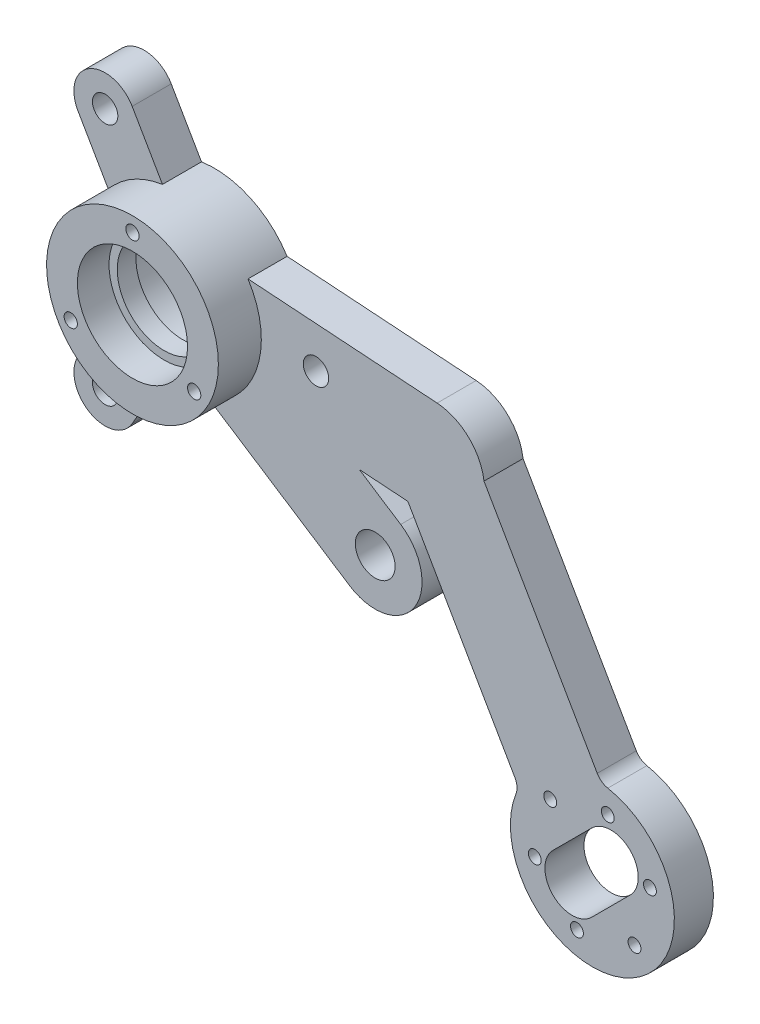
SolidWorks part; units mm, degrees
ref_plane "Front Plane" through (0, 0, 0) normal (0, 0, 1) x (1, 0, 0)
ref_plane "Top Plane" through (0, 0, 0) normal (0, 1, 0) x (1, 0, 0)
ref_plane "Right Plane" through (0, 0, 0) normal (1, 0, 0) x (0, 0, -1)
sketch "S01 - Bearing barrel" plane through (0, 0, 0) normal (0, 0, 1) x (1, 0, 0)
  circle A0 centre (0, 0) radius 22
  dimension "D1" = 44
extrude "01 - Bearing barrel" add sketch "S01 - Bearing barrel" along normal blind 21
sketch "S02 - Torque arm 1" plane through (0, 0, 0) normal (0, 0, 1) x (1, 0, 0)
  line L0 (0, 8) -> (36, 8)
  line L1 (36, -8) -> (0, -8)
  arc A0 (36, 8) -> (36, -8) centre (36, 0) cw
  arc A1 (0, -8) -> (0, 8) centre (0, 0) cw
  dimension "D1" = 8
  dimension "D2" = 36
extrude "02 - Torque arm 1" add sketch "S02 - Torque arm 1" along normal blind 10
sketch "S03 - Torque arm 2" plane through (0, 0, 0) normal (0, 0, 1) x (1, 0, 0)
  line L0 (-6.9282, -4) -> (-24.9282, 27.1769)
  line L1 (-11.0718, 35.1769) -> (6.9282, 4)
  arc A0 (-24.9282, 27.1769) -> (-11.0718, 35.1769) centre (-18, 31.1769) cw
  arc A1 (6.9282, 4) -> (-6.9282, -4) centre (0, 0) cw
  dimension "D1" = 8
  dimension "D2" = 8
  dimension "D3" = 6.9282
  dimension "D4" = 6.9282
  dimension "D5" = 11.0718
  dimension "D6" = 18
  dimension "D7" = 24.9282
  dimension "D8" = 27.1769
extrude "03 - Torque arm 2" add sketch "S03 - Torque arm 2" along normal blind 10
sketch "S04 - Torque arm 3" plane through (0, 0, 0) normal (0, 0, 1) x (1, 0, 0)
  line L0 (6.9282, -4) -> (-11.0718, -35.1769)
  line L1 (-24.9282, -27.1769) -> (-6.9282, 4)
  arc A0 (-11.0718, -35.1769) -> (-24.9282, -27.1769) centre (-18, -31.1769) cw
  arc A1 (-6.9282, 4) -> (6.9282, -4) centre (0, 0) cw
  dimension "D1" = 8
  dimension "D2" = 8
  dimension "D3" = 6.9282
  dimension "D4" = 6.9282
  dimension "D5" = 11.0718
  dimension "D6" = 18
  dimension "D7" = 24.9282
  dimension "D8" = 27.1769
extrude "04 - Torque arm 3" add sketch "S04 - Torque arm 3" along normal blind 10
sketch "S05 - Wheel arm root to rounded elbow" plane through (0, 0, 0) normal (0, 0, 1) x (1, 0, 0)
  line L0 (0.8909, 12.9694) -> (67.0223, 8.4265)
  line L1 (65.2405, -17.5124) -> (-0.8909, -12.9694)
  arc A0 (67.0223, 8.4265) -> (65.2405, -17.5124) centre (66.1314, -4.5429) cw
  arc A1 (-0.8909, -12.9694) -> (0.8909, 12.9694) centre (0, 0) cw
  dimension "D1" = 13
  dimension "D2" = 13
  dimension "D3" = 0.8909
  dimension "D4" = 65.2405
  dimension "D5" = 66.1314
  dimension "D6" = 67.0223
  dimension "D7" = 0.8909
  dimension "D8" = 8.4265
extrude "05 - Wheel arm root to rounded elbow" add sketch "S05 - Wheel arm root to rounded elbow" along normal blind 10
sketch "S06 - Long dropped wheel arm" plane through (0, 0, 0) normal (0, 0, 1) x (1, 0, 0)
  line L0 (76.5281, 1.4494) -> (116.8865, -68.5726)
  line L1 (96.093, -80.5573) -> (55.7347, -10.5353)
  arc A0 (116.8865, -68.5726) -> (96.093, -80.5573) centre (106.4898, -74.5649) cw
  arc A1 (55.7347, -10.5353) -> (76.5281, 1.4494) centre (66.1314, -4.5429) cw
  dimension "D1" = 12
  dimension "D2" = 12
  dimension "D3" = 55.7347
  dimension "D4" = 66.1314
  dimension "D5" = 76.5281
  dimension "D6" = 96.093
  dimension "D7" = 106.4898
  dimension "D8" = 116.8865
  dimension "D9" = 1.4494
  dimension "D10" = 68.5726
extrude "06 - Long dropped wheel arm" add sketch "S06 - Long dropped wheel arm" along normal blind 10
sketch "S07 - Broad cam follower mounting lug" plane through (0, 0, 0) normal (0, 0, 1) x (1, 0, 0)
  line L0 (6.5357, 10.064) -> (57.6946, -23.1589)
  line L1 (44.6232, -43.287) -> (-6.5357, -10.064)
  arc A0 (57.6946, -23.1589) -> (44.6232, -43.287) centre (51.1589, -33.223) cw
  arc A1 (-6.5357, -10.064) -> (6.5357, 10.064) centre (0, 0) cw
  dimension "D1" = 12
  dimension "D2" = 12
  dimension "D3" = 6.5357
  dimension "D4" = 44.6232
  dimension "D5" = 51.1589
  dimension "D6" = 57.6946
  dimension "D7" = 6.5357
  dimension "D8" = 23.1589
extrude "07 - Broad cam follower mounting lug" add sketch "S07 - Broad cam follower mounting lug" along normal blind 10
sketch "S08 - Bearing through relief" plane through (0, 0, 0) normal (0, 0, 1) x (1, 0, 0)
  circle A0 centre (0, 0) radius 12
  dimension "D1" = 24
extrude "08 - Bearing through relief" cut sketch "S08 - Bearing through relief" along normal blind 23 from offset 1 offset against normal yes
sketch "S09 - Inboard 6001 seat" plane through (0, 0, 0) normal (0, 0, 1) x (1, 0, 0)
  circle A0 centre (0, 0) radius 14.1
  dimension "D1" = 28.2
extrude "09 - Inboard 6001 seat" cut sketch "S09 - Inboard 6001 seat" along normal blind 8.2 from offset 0.1 offset against normal yes
sketch "S10 - Outboard 6001 seat" plane through (0, 0, 0) normal (0, 0, 1) x (1, 0, 0)
  circle A0 centre (0, 0) radius 14.1
  dimension "D1" = 28.2
extrude "10 - Outboard 6001 seat" cut sketch "S10 - Outboard 6001 seat" along normal blind 8.2 from offset 12.9
sketch "S11 - Keeper screws" plane through (0, 0, 0) normal (0, 0, 1) x (1, 0, 0)
  circle A0 centre (0, 18.25) radius 1.7
  circle A1 centre (-15.805, -9.125) radius 1.7
  circle A2 centre (15.805, -9.125) radius 1.7
  dimension "D1" = 3.4
  dimension "D2" = 3.4
  dimension "D3" = 3.4
  dimension "D4" = 15.805
  dimension "D5" = 15.805
  dimension "D6" = 18.25
  dimension "D7" = 9.125
extrude "11 - Keeper screws" cut sketch "S11 - Keeper screws" along normal blind 23 from offset 1 offset against normal yes
sketch "S12 - Torque pin retaining stems" plane through (0, 0, 0) normal (0, 0, 1) x (1, 0, 0)
  circle A0 centre (36, 0) radius 3.25
  circle A1 centre (-18, 31.1769) radius 3.25
  circle A2 centre (-18, -31.1769) radius 3.25
  dimension "D1" = 6.5
  dimension "D2" = 6.5
  dimension "D3" = 6.5
  dimension "D4" = 36
  dimension "D5" = 18
  dimension "D6" = 31.1769
  dimension "D7" = 31.1769
extrude "12 - Torque pin retaining stems" cut sketch "S12 - Torque pin retaining stems" along normal blind 12 from offset 1 offset against normal yes
sketch "S13 - Wheel tip through-bolt land" plane through (0, 0, 0) normal (0, 0, 1) x (1, 0, 0)
  circle A0 centre (106.4898, -74.5649) radius 21
  dimension "D1" = 42
  dimension "D2" = 106.4898
  dimension "D3" = 74.5649
extrude "13 - Wheel tip through-bolt land" [suppressed] add sketch "S13 - Wheel tip through-bolt land" along normal blind 10
sketch "S14 - Inboard 6808 inner-race shoulder" plane through (0, 0, 0) normal (0, 0, 1) x (1, 0, 0)
  circle A0 centre (106.4898, -74.5649) radius 21
  dimension "D1" = 42
  dimension "D2" = 106.4898
  dimension "D3" = 74.5649
extrude "14 - Inboard 6808 inner-race shoulder" [suppressed] add sketch "S14 - Inboard 6808 inner-race shoulder" along normal blind 7 from offset 10
sketch "S19 - Through bore for steel follower bush" plane through (0, 0, 0) normal (0, 0, 1) x (1, 0, 0)
  circle A0 centre (51.1589, -33.223) radius 5.1
  dimension "D1" = 10.2
  dimension "D2" = 51.1589
  dimension "D3" = 33.223
extrude "19 - Through bore for steel follower bush" cut sketch "S19 - Through bore for steel follower bush" along normal blind 12 from offset 1 offset against normal yes
sketch "S20 - Flush seat for bush flange" plane through (0, 0, 0) normal (0, 0, 1) x (1, 0, 0)
  circle A0 centre (51.1589, -33.223) radius 7.6
  dimension "D1" = 15.2
  dimension "D2" = 51.1589
  dimension "D3" = 33.223
extrude "20 - Flush seat for bush flange" cut sketch "S20 - Flush seat for bush flange" along normal blind 2.1 from offset 0.1 offset against normal yes
sketch "Sketch2" plane through (0, 0, 0) normal (0, 0, -1) x (-1, 0, 0)
  circle A3 centre (-102.8291, -90.4936) radius 1.5
  circle A4 centre (-92.3853, -80.4032) radius 1.5
  circle A5 centre (-117.574, -86.5427) radius 1.5
  circle A6 centre (-121.5249, -71.7978) radius 1.5
  circle A7 centre (-110.7309, -61.0038) radius 1.5
  circle A8 centre (-95.986, -64.9547) radius 1.5
  dimension "D1" = 3
  dimension "D2" = 3
extrude "Cut-Extrude1" [suppressed] cut sketch "Sketch2" against normal through all
sketch "Sketch7" [suppressed] plane through (0, 0, 17) normal (0, 0, 1) x (1, 0, 0)
  line L2 (109.2383, -68.1271) -> (125.8225, -75.2075)
  line L4 (107.1846, -78.4924) -> (99.515, -75.1591)
  arc A0 (109.2383, -68.1271) -> (99.515, -75.1591) centre (106.4898, -74.5649) ccw
  arc A1 (107.1846, -78.4924) -> (125.8225, -75.2075) centre (114.0208, -62.7631) ccw
  dimension "D1" = 14
  dimension "D2" = 14
  dimension "D4" = 7
  dimension "D5" = 18.9252
extrude "Cut-Extrude2" [suppressed] cut sketch "Sketch7" against normal through all
sketch "Johnson gearbox mounting flange layout" plane through (0, 0, 0) normal (0, 0, 1) x (1, 0, 0)
  circle A0 centre (102.4898, -67.6367) radius 21.6
extrude "Johnson gearbox mounting flange" [suppressed] add sketch "Johnson gearbox mounting flange layout" along normal blind 14
sketch "Recessed gearbox seat layout" plane through (0, 0, 0) normal (0, 0, 1) x (1, 0, 0)
  circle A0 centre (102.4898, -67.6367) radius 18.8
extrude "Recessed gearbox seat" [suppressed] cut sketch "Recessed gearbox seat layout" against normal blind 9.6 from offset 9.5
sketch "Output pilot on wheel axis layout" plane through (0, 0, 0) normal (0, 0, 1) x (1, 0, 0)
  circle A0 centre (106.4898, -74.5649) radius 6.2
extrude "Output pilot on wheel axis" [suppressed] cut sketch "Output pilot on wheel axis layout" against normal blind 7.65 from offset 17.1
sketch "Four M3 gearbox clearance holes layout" plane through (0, 0, 0) normal (0, 0, 1) x (1, 0, 0)
  circle A0 centre (115.7096, -75.2692) radius 1.65
  circle A1 centre (102.4898, -52.3717) radius 1.65
  circle A2 centre (89.2699, -60.0042) radius 1.65
  circle A3 centre (102.4898, -82.9017) radius 1.65
extrude "Four M3 gearbox clearance holes" [suppressed] cut sketch "Four M3 gearbox clearance holes layout" against normal blind 7.65 from offset 17.1
sketch "Inner motor screw head seats layout" plane through (0, 0, 0) normal (0, 0, 1) x (1, 0, 0)
  circle A0 centre (115.7096, -75.2692) radius 3.15
  circle A1 centre (102.4898, -82.9017) radius 3.15
extrude "Inner motor screw head seats" [suppressed] cut sketch "Inner motor screw head seats layout" against normal blind 3.1 from offset 17.1
sketch "Outer low-profile screw seats layout" plane through (0, 0, 0) normal (0, 0, 1) x (1, 0, 0)
  circle A0 centre (102.4898, -52.3717) radius 3.15
  circle A1 centre (89.2699, -60.0042) radius 3.15
extrude "Outer low-profile screw seats" [suppressed] cut sketch "Outer low-profile screw seats layout" against normal blind 4.8 from offset 17.1
sketch "Coaxial journal for both 6808 wheel bearings layout" plane through (0, 0, 0) normal (0, 0, 1) x (1, 0, 0)
  circle A0 centre (106.4898, -74.5649) radius 19.98
  circle A1 centre (106.4898, -74.5649) radius 14
extrude "Coaxial journal for both 6808 wheel bearings" [suppressed] add sketch "Coaxial journal for both 6808 wheel bearings layout" along normal blind 19.95 from offset 17
sketch "Flat motor mounting pad layout" plane through (0, 0, 0) normal (0, 0, 1) x (1, 0, 0)
  circle A0 centre (106.78, -75.7487) radius 21
extrude "Flat motor mounting pad" add sketch "Flat motor mounting pad layout" along normal blind 10
fillet "R4 blends from arm into motor pad" radius 4 2 edges at (87.9561, -66.4396, 5) (108.9858, -54.8649, 5)
sketch "Original round-ended output slot layout" plane through (0, 0, 0) normal (0, 0, 1) x (1, 0, 0)
  line L0 (96.6684, -75.9608) -> (106.5679, -66.0613)
  line L1 (116.4674, -75.9608) -> (106.5679, -85.8603)
  arc A0 (106.5679, -66.0613) -> (116.4674, -75.9608) centre (111.5176, -71.0111) cw
  arc A1 (106.5679, -85.8603) -> (96.6684, -75.9608) centre (101.6181, -80.9106) cw
extrude "28 x 14 closed through slot for motor output" cut sketch "Original round-ended output slot layout" against normal blind 10.24 from offset 10.12
sketch "Six clearance holes from Johnson motor face layout" plane through (0, 0, 0) normal (0, 0, 1) x (1, 0, 0)
  circle A0 centre (92.0352, -79.6996) radius 1.65
  circle A1 centre (102.8291, -90.4936) radius 1.65
  circle A2 centre (117.574, -86.5427) radius 1.65
  circle A3 centre (121.5249, -71.7978) radius 1.65
  circle A4 centre (110.7309, -61.0038) radius 1.65
  circle A5 centre (95.986, -64.9547) radius 1.65
extrude "Six clearance holes from Johnson motor face" cut sketch "Six clearance holes from Johnson motor face layout" against normal blind 10.24 from offset 10.12
